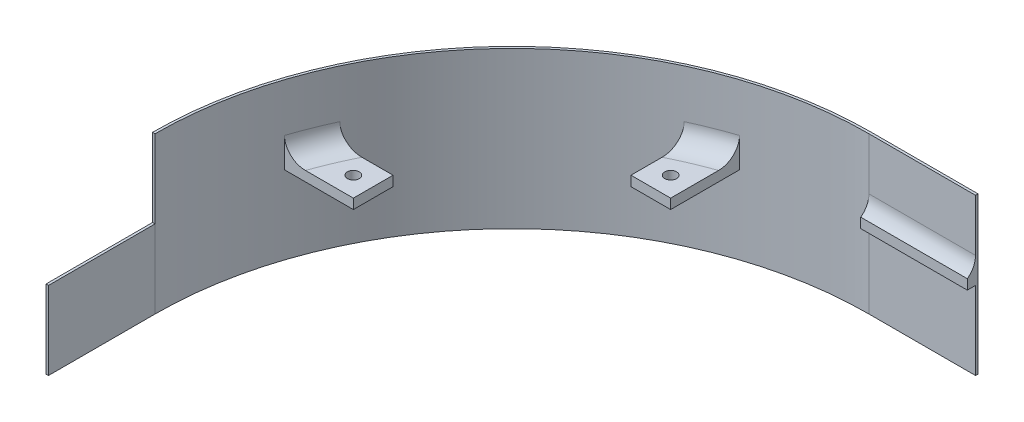
SolidWorks part; units mm, degrees
ref_plane "Front Plane" through (0, 0, 0) normal (0, 0, 1) x (1, 0, 0)
ref_plane "Top Plane" through (0, 0, 0) normal (0, 1, 0) x (1, 0, 0)
ref_plane "Right Plane" through (0, 0, 0) normal (1, 0, 0) x (0, 0, -1)
sketch "Sketch1" plane through (0, 0, 0) normal (0, 1, 0) x (1, 0, 0)
  line L1 (-34.1312, -148.4312) -> (34.1313, -148.4312)
  line L2 (-148.4312, -34.1312) -> (-148.4312, 34.1313)
  line L3 (-34.1312, 148.4313) -> (34.1313, 148.4313)
  line L4 (148.4312, -34.1312) -> (148.4312, 34.1313)
  line L5 (-148.4312, -148.4312) -> (148.4313, 148.4312) construction
  line L6 (-148.4312, 148.4312) -> (148.4313, -148.4312) construction
  arc A1 (-34.1312, -148.4312) -> (-148.4312, -34.1312) centre (-34.1312, -34.1312) cw
  arc A2 (34.1313, -148.4312) -> (148.4312, -34.1312) centre (34.1313, -34.1312) ccw
  arc A3 (34.1313, 148.4313) -> (148.4312, 34.1313) centre (34.1313, 34.1313) cw
  arc A4 (-148.4312, 34.1313) -> (-34.1312, 148.4313) centre (-34.1312, 34.1313) cw
  point P0 (0, 0)
  dimension "D1" = 296.8625
  dimension "D3" = 114.3
  dimension "D2" = 296.8625
extrude "Boss-Extrude1" add sketch "Sketch1" along normal blind 6.35
sketch "Sketch4" plane through (0, 6.35, 0) normal (0, 1, 0) x (1, 0, 0)
  line L0 (-39.448, -144.217) -> (39.448, -144.217)
  line L1 (-39.448, -120.2902) -> (39.448, -120.2902)
  line L2 (-39.448, 120.2902) -> (39.448, 120.2902)
  line L3 (-39.448, 144.217) -> (39.448, 144.217)
  line L4 (-39.448, 118.7027) -> (39.448, 118.7027)
  line L5 (-39.448, 145.8045) -> (39.448, 145.8045)
  line L6 (-39.448, -145.8045) -> (39.448, -145.8045)
  line L7 (-39.448, -118.7027) -> (39.448, -118.7027)
  line L8 (-13.125, 107.0625) -> (-13.125, 100.3125) construction
  line L9 (-13.125, 100.3125) -> (-18.875, 100.3125) construction
  line L10 (-18.875, 100.3125) -> (-18.875, 107.0625) construction
  line L11 (-18.875, 107.0625) -> (-13.125, 107.0625) construction
  line L12 (18.875, 107.0625) -> (18.875, 100.3125) construction
  line L13 (18.875, 100.3125) -> (13.125, 100.3125) construction
  line L14 (13.125, 100.3125) -> (13.125, 107.0625) construction
  line L15 (13.125, 107.0625) -> (18.875, 107.0625) construction
  line L16 (-7, 56.325) -> (-13, 56.325) construction
  line L17 (-13, 56.325) -> (-13, 64.325) construction
  line L18 (-13, 64.325) -> (-7, 64.325) construction
  line L19 (-7, 64.325) -> (-7, 56.325) construction
  line L20 (25, 56.325) -> (19, 56.325) construction
  line L21 (19, 56.325) -> (19, 64.325) construction
  line L22 (19, 64.325) -> (25, 64.325) construction
  line L23 (25, 64.325) -> (25, 56.325) construction
  line L24 (-13, -56.325) -> (-7, -56.325) construction
  line L25 (-7, -56.325) -> (-7, -64.325) construction
  line L26 (-7, -64.325) -> (-13, -64.325) construction
  line L27 (-13, -64.325) -> (-13, -56.325) construction
  line L28 (19, -56.325) -> (25, -56.325) construction
  line L29 (25, -56.325) -> (25, -64.325) construction
  line L30 (25, -64.325) -> (19, -64.325) construction
  line L31 (19, -64.325) -> (19, -56.325) construction
  line L32 (-18.875, -107.0625) -> (-18.875, -100.3125) construction
  line L33 (-18.875, -100.3125) -> (-13.125, -100.3125) construction
  line L34 (-13.125, -100.3125) -> (-13.125, -107.0625) construction
  line L35 (-13.125, -107.0625) -> (-18.875, -107.0625) construction
  line L36 (13.125, -107.0625) -> (13.125, -100.3125) construction
  line L37 (13.125, -100.3125) -> (18.875, -100.3125) construction
  line L38 (18.875, -100.3125) -> (18.875, -107.0625) construction
  line L39 (18.875, -107.0625) -> (13.125, -107.0625) construction
  line L40 (-13.125, 107.0625) -> (-13.125, 100.3125)
  line L41 (-13.125, 100.3125) -> (-18.875, 100.3125)
  line L42 (-18.875, 100.3125) -> (-18.875, 107.0625)
  line L43 (-18.875, 107.0625) -> (-13.125, 107.0625)
  line L44 (18.875, 107.0625) -> (18.875, 100.3125)
  line L45 (18.875, 100.3125) -> (13.125, 100.3125)
  line L46 (13.125, 100.3125) -> (13.125, 107.0625)
  line L47 (13.125, 107.0625) -> (18.875, 107.0625)
  line L48 (-7, 56.325) -> (-13, 56.325)
  line L49 (-13, 56.325) -> (-13, 64.325)
  line L50 (-13, 64.325) -> (-7, 64.325)
  line L51 (-7, 64.325) -> (-7, 56.325)
  line L52 (25, 56.325) -> (19, 56.325)
  line L53 (19, 56.325) -> (19, 64.325)
  line L54 (19, 64.325) -> (25, 64.325)
  line L55 (25, 64.325) -> (25, 56.325)
  line L56 (-13, -56.325) -> (-7, -56.325)
  line L57 (-7, -56.325) -> (-7, -64.325)
  line L58 (-7, -64.325) -> (-13, -64.325)
  line L59 (-13, -64.325) -> (-13, -56.325)
  line L60 (19, -56.325) -> (25, -56.325)
  line L61 (25, -56.325) -> (25, -64.325)
  line L62 (25, -64.325) -> (19, -64.325)
  line L63 (19, -64.325) -> (19, -56.325)
  line L64 (-18.875, -107.0625) -> (-18.875, -100.3125)
  line L65 (-18.875, -100.3125) -> (-13.125, -100.3125)
  line L66 (-13.125, -100.3125) -> (-13.125, -107.0625)
  line L67 (-13.125, -107.0625) -> (-18.875, -107.0625)
  line L68 (13.125, -107.0625) -> (13.125, -100.3125)
  line L69 (13.125, -100.3125) -> (18.875, -100.3125)
  line L70 (18.875, -100.3125) -> (18.875, -107.0625)
  line L71 (18.875, -107.0625) -> (13.125, -107.0625)
  line L72 (-18.875, -107.0625) -> (-13.125, -100.3125) construction
  line L73 (13.125, -107.0625) -> (18.875, -100.3125) construction
  line L74 (-13, -64.325) -> (-7, -56.325) construction
  line L75 (19, -64.325) -> (25, -56.325) construction
  line L76 (-13, 56.325) -> (-7, 64.325) construction
  line L77 (19, 56.325) -> (25, 64.325) construction
  line L78 (13.125, 100.3125) -> (18.875, 107.0625) construction
  line L79 (-18.875, 100.3125) -> (-13.125, 107.0625) construction
  arc A0 (58.6792, -125.8296) -> (39.448, -120.2902) centre (39.448, -156.4424) ccw construction
  arc A1 (58.6792, -138.6776) -> (58.6792, -125.8296) centre (54.6436, -132.2536) ccw construction
  arc A2 (39.448, -144.217) -> (58.6792, -138.6776) centre (39.448, -108.0647) ccw construction
  arc A3 (-39.448, -120.2902) -> (-58.6792, -125.8296) centre (-39.448, -156.4424) ccw construction
  arc A4 (-58.6792, -125.8296) -> (-58.6792, -138.6776) centre (-54.6436, -132.2536) ccw construction
  arc A5 (-58.6792, -138.6776) -> (-39.448, -144.217) centre (-39.448, -108.0647) ccw construction
  arc A6 (-58.6792, 125.8296) -> (-39.448, 120.2902) centre (-39.448, 156.4424) ccw construction
  arc A7 (-58.6792, 138.6776) -> (-58.6792, 125.8296) centre (-54.6436, 132.2536) ccw construction
  arc A8 (-39.448, 144.217) -> (-58.6792, 138.6776) centre (-39.448, 108.0647) ccw construction
  arc A9 (58.6792, 138.6776) -> (39.448, 144.217) centre (39.448, 108.0647) ccw construction
  arc A10 (58.6792, 125.8296) -> (58.6792, 138.6776) centre (54.6436, 132.2536) ccw construction
  arc A11 (39.448, 120.2902) -> (58.6792, 125.8296) centre (39.448, 156.4424) ccw construction
  arc A12 (58.6792, -125.8296) -> (39.448, -120.2902) centre (39.448, -156.4424) ccw
  arc A13 (58.6792, -138.6776) -> (58.6792, -125.8296) centre (54.6436, -132.2536) ccw
  arc A14 (39.448, -144.217) -> (58.6792, -138.6776) centre (39.448, -108.0647) ccw
  arc A15 (-39.448, -120.2902) -> (-58.6792, -125.8296) centre (-39.448, -156.4424) ccw
  arc A16 (-58.6792, -125.8296) -> (-58.6792, -138.6776) centre (-54.6436, -132.2536) ccw
  arc A17 (-58.6792, -138.6776) -> (-39.448, -144.217) centre (-39.448, -108.0647) ccw
  arc A18 (-58.6792, 125.8296) -> (-39.448, 120.2902) centre (-39.448, 156.4424) ccw
  arc A19 (-58.6792, 138.6776) -> (-58.6792, 125.8296) centre (-54.6436, 132.2536) ccw
  arc A20 (-39.448, 144.217) -> (-58.6792, 138.6776) centre (-39.448, 108.0647) ccw
  arc A21 (58.6792, 138.6776) -> (39.448, 144.217) centre (39.448, 108.0647) ccw
  arc A22 (58.6792, 125.8296) -> (58.6792, 138.6776) centre (54.6436, 132.2536) ccw
  arc A23 (39.448, 120.2902) -> (58.6792, 125.8296) centre (39.448, 156.4424) ccw
  arc A24 (-59.5236, 124.4853) -> (-39.448, 118.7027) centre (-39.448, 156.4424) ccw
  arc A25 (39.448, 118.7027) -> (59.5236, 124.4853) centre (39.448, 156.4424) ccw
  arc A26 (59.5236, 124.4853) -> (59.5236, 140.0219) centre (54.6436, 132.2536) ccw
  arc A27 (59.5236, 140.0219) -> (39.448, 145.8045) centre (39.448, 108.0647) ccw
  arc A28 (-39.448, 145.8045) -> (-59.5236, 140.0219) centre (-39.448, 108.0647) ccw
  arc A29 (-59.5236, 140.0219) -> (-59.5236, 124.4853) centre (-54.6436, 132.2536) ccw
  arc A30 (39.448, -145.8045) -> (59.5236, -140.0219) centre (39.448, -108.0647) ccw
  arc A31 (59.5236, -140.0219) -> (59.5236, -124.4853) centre (54.6436, -132.2536) ccw
  arc A32 (59.5236, -124.4853) -> (39.448, -118.7027) centre (39.448, -156.4424) ccw
  arc A33 (-39.448, -118.7027) -> (-59.5236, -124.4853) centre (-39.448, -156.4424) ccw
  arc A34 (-59.5236, -124.4853) -> (-59.5236, -140.0219) centre (-54.6436, -132.2536) ccw
  arc A35 (-59.5236, -140.0219) -> (-39.448, -145.8045) centre (-39.448, -108.0647) ccw
  point P58 (-16, -103.6875)
  point P60 (16, 103.6875)
  point P62 (-16, 103.6875)
  point P63 (-10, 60.325)
  point P66 (22, 60.325)
  point P68 (-10, -60.325)
  point P70 (16, -103.6875)
  point P71 (22, -60.325)
  dimension "D1" = 1.5875
extrude "Cut-Extrude1" cut sketch "Sketch4" against normal blind 6.35 contours L2 A23 A22 A21 L3 A20 A19 A18 | A28 A29 A24 L4 A25 A26 A27 L5 A23 L2 A18 A19 A20 L3 A21 A22 | A16 A17 L0 A14 A13 A12 L1 A15 | A34 A35 L6 A30 A31 A32 L7 A33 A17 A16 A15 L1 A12 A13 A14 L0 region at (0, 6.35, 132.2536) region at (0, 6.35, -132.2536) region at (-49.5328, 6.35, -121.431) region at (-49.5328, 6.35, 143.0762)
hole_wizard "M4 Clearance Hole1" positions "Sketch7" profile "Sketch9" hole size "M4" standard "ANSI Metric" end condition through all
sketch "Sketch7" plane through (0, 6.35, 0) normal (0, 1, 0) x (1, 0, 0)
  point P0 (-16, -103.6875)
  point P3 (16, -103.6875)
  point P6 (22, -60.325)
  point P9 (-10, -60.325)
  point P12 (-10, 60.325)
  point P15 (22, 60.325)
  point P18 (16, 103.6875)
  point P21 (-16, 103.6875)
sketch "Sketch9" plane through (-16, 6.35, 103.6875) normal (1, 0, 0) x (0, 0, 1)
  line L0 (0, 0) -> (0, 6.35)
  line L1 (0, 6.35) -> (2.25, 6.35)
  line L2 (2.25, 6.35) -> (2.25, 0)
  line L5 (2.25, 0) -> (0, 0)
  line L11 (0, -6.35) -> (0, 107.95) construction
  dimension "Thru Hole Dia." = 4.5
  dimension "Thru Hole Depth" = 6.35
sketch "Sketch11" plane through (0, 6.35, 0) normal (0, 1, 0) x (1, 0, 0)
  line L1 (101.6, 101.6) -> (-101.6, 101.6)
  line L2 (101.6, 101.6) -> (101.6, -101.6)
  line L3 (101.6, -101.6) -> (-101.6, -101.6)
  line L4 (-101.6, 101.6) -> (-101.6, -101.6)
  line L5 (101.6, 101.6) -> (-101.6, -101.6) construction
  line L6 (101.6, -101.6) -> (-101.6, 101.6) construction
  circle A0 centre (0, 0) radius 143.6841 construction
  point P7 (-127, -101.6)
  point P10 (-127, 101.6)
  point P11 (-127, -76.2)
  point P12 (-127, -50.8)
  point P13 (-127, -25.4)
  point P14 (-127, 0)
  point P15 (-127, 25.4)
  point P16 (-127, 50.8)
  point P17 (-127, 76.2)
  point P18 (-101.6, -101.6)
  point P19 (-101.6, 101.6)
  point P20 (-101.6, -76.2)
  point P21 (-101.6, -50.8)
  point P22 (-101.6, -25.4)
  point P23 (-101.6, 0)
  point P24 (-101.6, 25.4)
  point P25 (-101.6, 50.8)
  point P26 (-101.6, 76.2)
  point P27 (-76.2, -101.6)
  point P28 (-76.2, 101.6)
  point P29 (-76.2, -76.2)
  point P30 (-76.2, -50.8)
  point P31 (-76.2, -25.4)
  point P32 (-76.2, 0)
  point P33 (-76.2, 25.4)
  point P34 (-76.2, 50.8)
  point P35 (-76.2, 76.2)
  point P36 (-50.8, -101.6)
  point P37 (-50.8, 101.6)
  point P38 (-50.8, -76.2)
  point P39 (-50.8, -50.8)
  point P40 (-50.8, -25.4)
  point P41 (-50.8, 0)
  point P42 (-50.8, 25.4)
  point P43 (-50.8, 50.8)
  point P44 (-50.8, 76.2)
  point P45 (-25.4, -101.6)
  point P46 (-25.4, 101.6)
  point P47 (-25.4, -76.2)
  point P48 (-25.4, -50.8)
  point P49 (-25.4, -25.4)
  point P50 (-25.4, 0)
  point P51 (-25.4, 25.4)
  point P52 (-25.4, 50.8)
  point P53 (-25.4, 76.2)
  point P54 (0, -101.6)
  point P55 (0, 101.6)
  point P56 (0, -76.2)
  point P57 (0, -50.8)
  point P58 (0, -25.4)
  point P59 (0, 0)
  point P60 (0, 25.4)
  point P61 (0, 50.8)
  point P62 (0, 76.2)
  point P63 (25.4, -101.6)
  point P64 (25.4, 101.6)
  point P65 (25.4, -76.2)
  point P66 (25.4, -50.8)
  point P67 (25.4, -25.4)
  point P68 (25.4, 0)
  point P69 (25.4, 25.4)
  point P70 (25.4, 50.8)
  point P71 (25.4, 76.2)
  point P72 (50.8, -101.6)
  point P73 (50.8, 101.6)
  point P74 (50.8, -76.2)
  point P75 (50.8, -50.8)
  point P76 (50.8, -25.4)
  point P77 (50.8, 0)
  point P78 (50.8, 25.4)
  point P79 (50.8, 50.8)
  point P80 (50.8, 76.2)
  point P81 (76.2, -101.6)
  point P82 (76.2, 101.6)
  point P83 (76.2, -76.2)
  point P84 (76.2, -50.8)
  point P85 (76.2, -25.4)
  point P86 (76.2, 0)
  point P87 (76.2, 25.4)
  point P88 (76.2, 50.8)
  point P89 (76.2, 76.2)
  point P90 (101.6, -101.6)
  point P91 (101.6, 101.6)
  point P92 (101.6, -76.2)
  point P93 (101.6, -50.8)
  point P94 (101.6, -25.4)
  point P95 (101.6, 0)
  point P96 (101.6, 25.4)
  point P97 (101.6, 50.8)
  point P98 (101.6, 76.2)
  point P99 (127, -101.6)
  point P100 (127, 101.6)
  point P101 (127, -76.2)
  point P102 (127, -50.8)
  point P103 (127, -25.4)
  point P104 (127, 0)
  point P105 (127, 25.4)
  point P106 (127, 50.8)
  point P107 (127, 76.2)
  dimension "D1" = 203.2
  dimension "D2" = 25.4
  dimension "D3" = 11
  dimension "D4" = 9
hole_wizard "#6 Clearance Hole1" positions "Sketch12" profile "Sketch13" hole size "#6" standard "ANSI Inch" end condition through all
sketch "Sketch12" plane through (0, 6.35, 0) normal (0, 1, 0) x (1, 0, 0)
  point P0 (-101.6, -101.6)
  point P3 (-101.6, 101.6)
  point P6 (101.6, 101.6)
  point P9 (101.6, -101.6)
  point P12 (-127, -76.2)
  point P15 (-127, -50.8)
  point P18 (-127, 50.8)
  point P21 (-127, 76.2)
  point P24 (-101.6, 76.2)
  point P27 (-101.6, 50.8)
  point P30 (-101.6, 25.4)
  point P33 (-101.6, 0)
  point P36 (-101.6, -25.4)
  point P39 (-101.6, -50.8)
  point P42 (-101.6, -76.2)
  point P45 (-76.2, -101.6)
  point P48 (-50.8, -101.6)
  point P51 (-50.8, -76.2)
  point P54 (-76.2, -76.2)
  point P57 (-76.2, -50.8)
  point P60 (-50.8, -50.8)
  point P63 (-50.8, -25.4)
  point P66 (-76.2, -25.4)
  point P69 (-76.2, 0)
  point P72 (-50.8, 0)
  point P75 (-50.8, 25.4)
  point P78 (-76.2, 25.4)
  point P81 (-76.2, 50.8)
  point P84 (-50.8, 50.8)
  point P87 (-50.8, 76.2)
  point P90 (-76.2, 76.2)
  point P93 (-76.2, 101.6)
  point P96 (-50.8, 101.6)
  point P99 (50.8, -101.6)
  point P102 (76.2, -101.6)
  point P105 (101.6, -76.2)
  point P108 (127, -76.2)
  point P111 (127, -50.8)
  point P114 (101.6, -25.4)
  point P117 (101.6, -50.8)
  point P120 (76.2, -25.4)
  point P123 (76.2, -50.8)
  point P126 (76.2, -76.2)
  point P129 (50.8, -76.2)
  point P132 (50.8, -50.8)
  point P135 (50.8, -25.4)
  point P138 (50.8, 0)
  point P141 (76.2, 0)
  point P144 (101.6, 0)
  point P147 (101.6, 25.4)
  point P150 (101.6, 50.8)
  point P153 (101.6, 76.2)
  point P156 (127, 50.8)
  point P159 (127, 76.2)
  point P162 (76.2, 101.6)
  point P165 (50.8, 101.6)
  point P168 (50.8, 76.2)
  point P171 (76.2, 76.2)
  point P174 (76.2, 50.8)
  point P177 (76.2, 25.4)
  point P180 (50.8, 25.4)
  point P183 (50.8, 50.8)
  point P186 (0, 0)
  point P189 (-25.4, -25.4)
  point P192 (-25.4, 0)
  point P195 (-25.4, 25.4)
  point P198 (0, 25.4)
  point P201 (25.4, 25.4)
  point P204 (25.4, 0)
  point P207 (25.4, -25.4)
  point P210 (0, -25.4)
  point P213 (127, -25.4)
  point P216 (127, 0)
  point P219 (127, 25.4)
  point P222 (-127, -25.4)
  point P225 (-127, 0)
  point P228 (-127, 25.4)
sketch "Sketch13" plane through (-101.6, 6.35, 101.6) normal (1, 0, 0) x (0, 0, 1)
  line L0 (0, 0) -> (0, 6.35)
  line L1 (0, 6.35) -> (1.8986, 6.35)
  line L2 (1.8986, 6.35) -> (1.8986, 0)
  line L5 (1.8986, 0) -> (0, 0)
  line L11 (0, -6.35) -> (0, 107.95) construction
  dimension "Thru Hole Dia." = 3.7973
  dimension "Thru Hole Depth" = 6.35
sketch "Sketch14" plane through (0, 6.35, 0) normal (0, 1, 0) x (1, 0, 0)
  line L1 (76.2, -127) -> (-76.2, -127)
  line L2 (76.2, -127) -> (76.2, 127)
  line L3 (76.2, 127) -> (-76.2, 127)
  line L4 (-76.2, -127) -> (-76.2, 127)
  line L5 (76.2, -127) -> (-76.2, 127) construction
  line L6 (76.2, 127) -> (-76.2, -127) construction
  circle A1 centre (-76.2, -101.6) radius 1.8986 construction
  circle A2 centre (-101.6, -101.6) radius 1.8986 construction
  point P0 (0, 0)
  dimension "D1" = 25.4
  dimension "D2" = 25.4
hole_wizard "#6 Clearance Hole2" positions "Sketch15" profile "Sketch16" hole size "#6" standard "ANSI Inch" end condition through all
sketch "Sketch15" plane through (0, 6.35, 0) normal (0, 1, 0) x (1, 0, 0)
  point P0 (-76.2, -127)
  point P3 (76.2, -127)
  point P6 (76.2, 127)
  point P9 (-76.2, 127)
sketch "Sketch16" plane through (-76.2, 6.35, 127) normal (1, 0, 0) x (0, 0, 1)
  line L0 (0, 0) -> (0, 6.35)
  line L1 (0, 6.35) -> (1.8986, 6.35)
  line L2 (1.8986, 6.35) -> (1.8986, 0)
  line L5 (1.8986, 0) -> (0, 0)
  line L11 (0, -6.35) -> (0, 107.95) construction
  dimension "Thru Hole Dia." = 3.7973
  dimension "Thru Hole Depth" = 6.35
sketch "Sketch29" plane through (0, 6.35, 0) normal (0, 1, 0) x (1, 0, 0)
  line L0 (-39.448, 145.8045) -> (39.448, 145.8045) construction
  line L1 (-148.4312, 34.1312) -> (-148.4312, -34.1312) construction
  line L2 (-34.1312, 148.4313) -> (0, 148.4313)
  line L3 (34.1313, 148.4313) -> (-34.1312, 148.4313) construction
  line L4 (-148.4312, 34.1312) -> (-148.4312, 0)
  line L5 (0, 148.4313) -> (-34.1312, 148.4313)
  line L6 (-69.85, 142.7068) -> (-69.85, 120.65)
  line L7 (-69.85, 120.65) -> (-82.55, 120.65)
  line L8 (-82.55, 120.65) -> (-82.55, 137.6692)
  line L9 (-137.6692, 82.55) -> (-120.65, 82.55)
  line L10 (-34.1312, -148.4312) -> (34.1313, -148.4312)
  line L11 (148.4313, -34.1312) -> (148.4312, 34.1313)
  line L12 (34.1313, 148.4313) -> (-34.1312, 148.4313)
  line L13 (-148.4312, 34.1312) -> (-148.4312, -34.1312)
  line L14 (-34.1312, 148.4313) -> (-34.1312, 145.8045)
  line L15 (-34.1312, 145.8045) -> (0, 145.8045)
  line L16 (0, 148.4313) -> (-34.1312, 148.4313)
  line L17 (-148.4312, 34.1312) -> (-148.4312, 0)
  line L18 (-120.65, 82.55) -> (-120.65, 69.85)
  line L19 (-120.65, 69.85) -> (-142.7068, 69.85)
  line L20 (0, 149.225) -> (-34.1312, 149.225)
  line L21 (-149.225, 34.1312) -> (-149.225, 0)
  line L22 (0, 148.4313) -> (0, 149.225)
  line L23 (-148.4312, 0) -> (-149.225, 0)
  line L24 (34.1313, 149.225) -> (-34.1312, 149.225) construction
  line L25 (34.1313, 148.4313) -> (-34.1312, 148.4313) construction
  line L26 (-149.225, 34.1312) -> (-149.225, -34.1312) construction
  line L27 (-148.4312, 34.1312) -> (-148.4312, -34.1312) construction
  line L28 (0, 148.4313) -> (0, 145.8045)
  line L30 (-148.4312, 34.1312) -> (-145.8045, 34.1312)
  line L31 (-148.4312, 34.1312) -> (-148.4312, 0)
  line L32 (-148.4312, 0) -> (-145.8045, 0)
  line L33 (-145.8045, 34.1312) -> (-145.8045, 0)
  arc A0 (-34.1312, 148.4313) -> (-148.4312, 34.1312) centre (-34.1312, 34.1313) ccw construction
  arc A1 (-34.1312, 148.4313) -> (-69.85, 142.7068) centre (-34.1312, 34.1313) ccw
  circle A2 centre (-127, 76.2) radius 1.8987 construction
  circle A3 centre (-76.2, 127) radius 1.8987 construction
  circle A4 centre (-127, 76.2) radius 1.8987
  circle A5 centre (-76.2, 127) radius 1.8987
  arc A6 (-34.1312, 149.225) -> (-149.225, 34.1313) centre (-34.1312, 34.1313) ccw
  arc A7 (-82.55, 137.6692) -> (-137.6692, 82.55) centre (-34.1312, 34.1313) ccw
  arc A8 (-34.1312, 148.4313) -> (-148.4312, 34.1312) centre (-34.1312, 34.1313) ccw construction
  arc A9 (-82.55, 137.6692) -> (-137.6692, 82.55) centre (-34.1312, 34.1313) ccw
  arc A10 (-148.4312, -34.1312) -> (-34.1312, -148.4312) centre (-34.1312, -34.1312) ccw
  arc A11 (34.1313, -148.4312) -> (148.4313, -34.1312) centre (34.1313, -34.1312) ccw
  arc A12 (148.4312, 34.1313) -> (34.1313, 148.4313) centre (34.1313, 34.1313) ccw
  arc A13 (-34.1312, 148.4313) -> (-148.4312, 34.1312) centre (-34.1312, 34.1313) ccw
  arc A14 (-142.7068, 69.85) -> (-148.4312, 34.1312) centre (-34.1312, 34.1313) ccw
  arc A15 (-142.7068, 69.85) -> (-148.4312, 34.1312) centre (-34.1312, 34.1313) ccw
  arc A16 (-34.1312, 148.4313) -> (-148.4312, 34.1312) centre (-34.1312, 34.1313) ccw
  arc A17 (-34.1312, 148.4313) -> (-69.85, 142.7068) centre (-34.1312, 34.1313) ccw
  point P31 (-76.2, 120.65)
  point P32 (-120.65, 76.2)
  dimension "D3" = 6.35
  dimension "D2" = 6.35
  dimension "D4" = 6.35
  dimension "D5" = 6.35
  dimension "D1" = 0
  dimension "D6" = 0.7937
sketch "Sketch30" plane through (0, 6.35, 0) normal (0, 1, 0) x (1, 0, 0)
  line L4 (-34.1312, -148.4312) -> (34.1313, -148.4312)
  line L5 (148.4313, -34.1312) -> (148.4312, 34.1313)
  line L6 (34.1313, 148.4313) -> (-34.1312, 148.4313)
  line L7 (-148.4312, 34.1313) -> (-148.4312, -34.1312)
  line L8 (-34.1312, -148.4312) -> (34.1313, -148.4312)
  line L9 (148.4313, -34.1312) -> (148.4312, 34.1313)
  line L10 (34.1313, 148.4313) -> (-34.1312, 148.4313)
  line L11 (-148.4312, 34.1313) -> (-148.4312, -34.1312)
  arc A4 (-148.4312, -34.1312) -> (-34.1312, -148.4312) centre (-34.1312, -34.1312) ccw
  arc A5 (34.1313, -148.4312) -> (148.4313, -34.1312) centre (34.1313, -34.1312) ccw
  arc A6 (148.4312, 34.1313) -> (34.1313, 148.4313) centre (34.1313, 34.1313) ccw
  arc A7 (-34.1312, 148.4313) -> (-148.4312, 34.1313) centre (-34.1312, 34.1313) ccw
  arc A8 (-148.4312, -34.1312) -> (-34.1312, -148.4312) centre (-34.1312, -34.1312) ccw
  arc A9 (34.1313, -148.4312) -> (148.4313, -34.1312) centre (34.1313, -34.1312) ccw
  arc A10 (148.4312, 34.1313) -> (34.1313, 148.4313) centre (34.1313, 34.1313) ccw
  arc A11 (-34.1312, 148.4313) -> (-148.4312, 34.1313) centre (-34.1312, 34.1313) ccw
  dimension "D1" = 0
extrude "Boss-Extrude4" add sketch "Sketch29" along normal blind 3.175 contours L6 A16 L8 L7 A5 | L9 A16 L19 L18 A4 | L33 L30 L4 L32 | L28 L2 L14 L15 region at (-17.0656, 6.35, -147.1179) region at (-75.9165, 6.35, -130.7143) region at (-130.7143, 6.35, -75.9165) region at (-147.1179, 6.35, -17.0656)
extrude "Cut-Extrude9" cut sketch "Sketch30" against normal through all
extrude "Boss-Extrude5" add sketch "Sketch29<7>" against normal blind 25 and the other way blind 25 contours A16 A1 L5 L22 L20 A6 L21 L23 L4 A14 A7 region at (-52.2519, 6.35, -147.1995)
sketch "Sketch29<7>" plane through (0, 6.35, 0) normal (0, 1, 0) x (1, 0, 0) same geometry as "Sketch29"
sketch "Sketch31" plane through (-145.8045, 0, 0) normal (1, 0, 0) x (0, 0, -1)
  line L4 (0, 6.35) -> (34.1312, 6.35)
  line L5 (34.1312, 6.35) -> (34.1312, 9.525)
  line L6 (34.1312, 9.525) -> (0, 9.525)
  line L7 (0, 9.525) -> (0, 6.35)
  line L8 (0, 6.35) -> (34.1312, 6.35)
  line L9 (34.1312, 6.35) -> (34.1312, 9.525)
  line L10 (34.1312, 9.525) -> (0, 9.525)
  line L11 (0, 9.525) -> (0, 6.35)
  dimension "D1" = 0
extrude "Boss-Extrude6" add sketch "Sketch31" against normal up to surface (3.4205 mm away) up to face at (-149.225, 6.35, -17.0656)
sketch "Sketch32" plane through (0, 0, -145.8045) normal (0, 0, 1) x (1, 0, 0)
  line L4 (-34.1313, 6.35) -> (0, 6.35)
  line L5 (0, 6.35) -> (0, 9.525)
  line L6 (0, 9.525) -> (-34.1313, 9.525)
  line L7 (-34.1313, 9.525) -> (-34.1313, 6.35)
  line L8 (-34.1313, 6.35) -> (0, 6.35)
  line L9 (0, 6.35) -> (0, 9.525)
  line L10 (0, 9.525) -> (-34.1313, 9.525)
  line L11 (-34.1313, 9.525) -> (-34.1313, 6.35)
  dimension "D1" = 0
extrude "Boss-Extrude7" add sketch "Sketch32" against normal up to surface (3.4205 mm away) up to face at (-17.0656, 6.35, -149.225)
fillet "Fillet2" radius 6.35 2 edges at (-76.2753, 9.525, -140.378) (-140.378, 9.525, -76.2753)
fillet "Fillet3" radius 6.35 2 edges at (-17.0656, 9.525, -148.4313) (-148.4312, 9.525, -17.0656)
sketch "Sketch33" plane through (-145.8045, 0, 0) normal (1, 0, 0) x (0, 0, -1)
  line L1 (34.1312, 6.35) -> (-28.52, 6.35)
  line L2 (34.1312, 6.35) -> (34.1312, 57.7302)
  line L3 (34.1312, 57.7302) -> (-28.52, 57.7302)
  line L4 (-28.52, 6.35) -> (-28.52, 57.7302)
extrude "Cut-Extrude10" cut sketch "Sketch33" against normal through all
